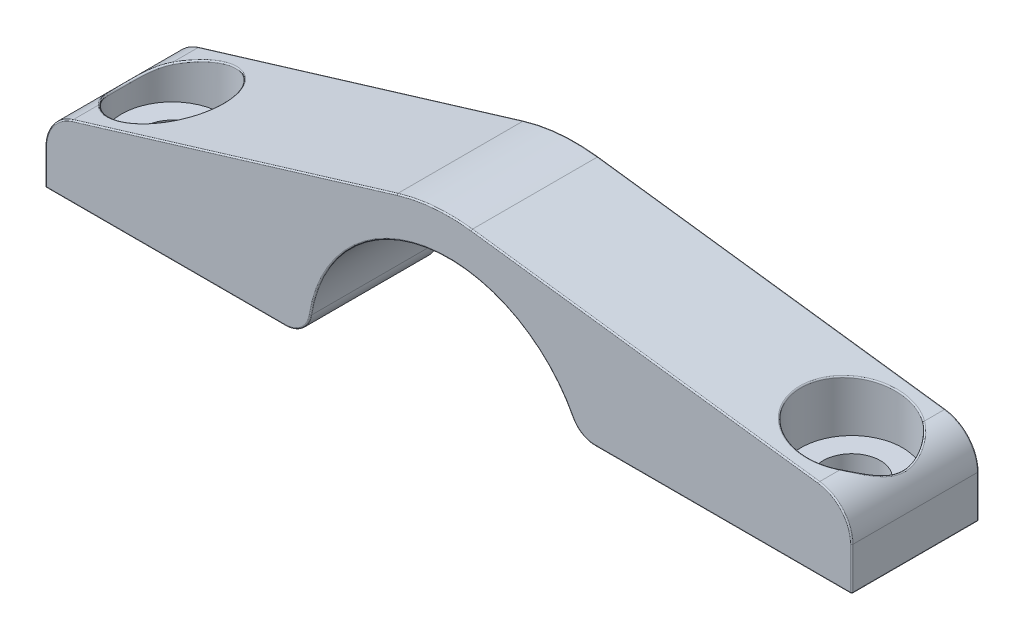
SolidWorks part; units mm, degrees
material "Сплав 2024"
ref_plane "Спереди" through (0, 0, 0) normal (0, 0, 1) x (1, 0, 0)
ref_plane "Сверху" through (0, 0, 0) normal (0, 1, 0) x (1, 0, 0)
ref_plane "Справа" through (0, 0, 0) normal (1, 0, 0) x (0, 0, -1)
sketch "Эскиз1" plane through (0, 0, 0) normal (0, 0, 1) x (1, 0, 0)
  line L0 (-50.7044, 0) -> (94.5195, 0) construction
  line L1 (0, 39.6279) -> (0, -47.9421) construction
  line L2 (-31.75, 5) -> (-4.0634, 13.3973)
  line L4 (-31.75, 5) -> (-31.75, 0)
  line L5 (-31.75, 0) -> (-11, 0)
  line L6 (31.75, 10) -> (31.75, 4)
  line L7 (-31.75, 5) -> (17.9945, 5) construction
  line L8 (-31.75, 0) -> (31.75, 10) construction
  line L9 (31.75, 10) -> (1.8004, 13.8838)
  line L10 (46.3702, 4) -> (-24.3242, 4) construction
  line L11 (31.75, 4) -> (10.247, 4)
  arc A0 (-11, 0) -> (10.247, 4) centre (0, 0) cw
  arc A1 (-4.0634, 13.3973) -> (1.8004, 13.8838) centre (0, 0) cw
  point P10 (0, 5)
  dimension "D1" = 11
  dimension "D2" = 3
  dimension "D3" = 63.5
  dimension "D4" = 5
  dimension "D5" = 31.75
  dimension "D6" = 4
  dimension "D7" = 6
extrude "Бобышка-Вытянуть1" add sketch "Эскиз1" along normal blind 10
fillet "Скругление1" [suppressed] radius 3
ref_plane "Плоскость1" through (0, 7, 0) normal (0, 1, 0) x (1, 0, 0)
sketch "Эскиз2" plane through (0, 7, 0) normal (0, 1, 0) x (1, 0, 0)
  line L0 (-31.75, -5) -> (-11, -5) construction
  line L1 (-31.75, -10) -> (-31.75, 0) construction
  line L2 (-11, -10) -> (-11, 0) construction
  line L3 (-26.75, -10) -> (-26.75, 0) construction
  dimension "D1" = 5
hole_wizard "Цековка для винта с внутренним шестигранником M42" positions "Эскиз6" profile "Эскиз5" counterbore size "M4" standard "Ansi Metric" end condition through all
sketch "Эскиз6" plane through (0, 7, 0) normal (0, 1, 0) x (1, 0, 0)
  line L0 (-31.75, -5) -> (-11, -5) construction
  line L1 (-26.75, -10) -> (-26.75, 0) construction
  point P0 (-26.75, -5)
sketch "Эскиз5" plane through (-26.75, 7, 5) normal (1, 0, 0) x (0, 0, -1)
  line L0 (0, 0) -> (0, 7)
  line L1 (0, 7) -> (2.25, 7)
  line L3 (2.25, 7) -> (2.25, 4)
  line L4 (2.25, 4) -> (4, 4)
  line L5 (4, 4) -> (4, 0)
  line L7 (4, 0) -> (0, 0)
  line L11 (0, -6.35) -> (0, 107.95) construction
  dimension "Диаметр сквозного отверстия" = 4.5
  dimension "Глубина сквозного отверстия" = 7
  dimension "Диаметр цековки" = 8
  dimension "Глубина цековки" = 4
hole_wizard "Цековка для винта с внутренним шестигранником M43" positions "Эскиз8" profile "Эскиз7" counterbore size "M4" standard "Ansi Metric" end condition through all
sketch "Эскиз8" plane through (0, 7, 0) normal (0, 1, 0) x (1, 0, 0)
  point P0 (-26.75, -5)
sketch "Эскиз7" plane through (-26.75, 7, 5) normal (1, 0, 0) x (0, 0, 1)
  line L0 (0, 0) -> (0, 7)
  line L1 (0, 7) -> (2.25, 7)
  line L3 (2.25, 7) -> (2.25, 4)
  line L4 (2.25, 4) -> (4, 4)
  line L5 (4, 4) -> (4, 0)
  line L7 (4, 0) -> (0, 0)
  line L11 (0, -6.35) -> (0, 107.95) construction
  dimension "Диаметр сквозного отверстия" = 4.5
  dimension "Глубина сквозного отверстия" = 7
  dimension "Диаметр цековки" = 8
  dimension "Глубина цековки" = 4
ref_plane "Плоскость2" through (0, 11, 0) normal (0, -1, 0) x (-1, 0, 0)
sketch "Эскиз9" plane through (0, 11, 0) normal (0, -1, 0) x (-1, 0, 0)
  line L0 (-31.75, -5) -> (-10.247, -5) construction
  line L1 (-31.75, -10) -> (-31.75, 0) construction
  line L2 (-10.247, -10) -> (-10.247, 0) construction
  line L3 (-26.75, 0) -> (-26.75, -10) construction
  dimension "D1" = 5
hole_wizard "Цековка для винта с внутренним шестигранником M44" positions "Эскиз11" profile "Эскиз10" counterbore size "M4" standard "Ansi Metric" end condition through all
sketch "Эскиз11" plane through (0, 11, 0) normal (0, -1, 0) x (-1, 0, 0)
  line L0 (-26.75, 0) -> (-26.75, -10) construction
  line L1 (-31.75, -5) -> (-10.247, -5) construction
  point P0 (-26.75, -5)
sketch "Эскиз10" plane through (26.75, 11, 5) normal (1, 0, 0) x (0, 0, 1)
  line L0 (0, 0) -> (0, 11)
  line L1 (0, 11) -> (2.25, 11)
  line L3 (2.25, 11) -> (2.25, 4)
  line L4 (2.25, 4) -> (4, 4)
  line L5 (4, 4) -> (4, 0)
  line L7 (4, 0) -> (0, 0)
  line L11 (0, -6.35) -> (0, 107.95) construction
  dimension "Диаметр сквозного отверстия" = 4.5
  dimension "Глубина сквозного отверстия" = 11
  dimension "Диаметр цековки" = 8
  dimension "Глубина цековки" = 4
hole_wizard "Цековка для винта с внутренним шестигранником M45" positions "Эскиз13" profile "Эскиз12" counterbore size "M4" standard "Ansi Metric" end condition through all
sketch "Эскиз13" plane through (0, 11, 0) normal (0, -1, 0) x (-1, 0, 0)
  line L0 (-31.75, -5) -> (-10.247, -5) construction
  line L1 (-26.75, 0) -> (-26.75, -10) construction
  point P0 (-26.75, -5)
sketch "Эскиз12" plane through (26.75, 11, 5) normal (1, 0, 0) x (0, 0, -1)
  line L0 (0, 0) -> (0, 3)
  line L1 (0, 3) -> (2.25, 3)
  line L3 (2.25, 3) -> (2.25, 4)
  line L4 (2.25, 4) -> (4, 4)
  line L5 (4, 4) -> (4, 0)
  line L7 (4, 0) -> (0, 0)
  line L11 (0, -6.35) -> (0, 107.95) construction
  dimension "Диаметр сквозного отверстия" = 4.5
  dimension "Глубина сквозного отверстия" = 3
  dimension "Диаметр цековки" = 8
  dimension "Глубина цековки" = 4
fillet "Скругление4" radius 2 2 edges at (10.247, 4, 5) (-11, 0, 5)
fillet "Скругление2" radius 3 2 edges at (-31.75, 5, 5) (31.75, 10, 5)
fillet "Скругление3" radius 0.1 32 edges at (30.7465, 9.6031, 5.1671) (-30.7258, 5.0324, 4.5607) (-31.75, 0, 5) (-26.75, 0, 7.25) (31.75, 4, 5) (24.5, 4, 5) (-22.2976, 0, 0) (-1.7811, 10.8548, 0) (21.6413, 4, 0) (31.75, 5.682, 0) (31.0036, 9.3441, 0) (15.4681, 12.1114, 0) (-1.1574, 13.9521, 0) (-16.8421, 9.5216, 0) (-31.1596, 4.5621, 0) (-31.75, 1.3875, 0) (-1.1574, 13.9521, 10) (15.4681, 12.1114, 10) (31.0036, 9.3441, 10) (31.75, 5.682, 10) (21.6413, 4, 10) (-1.7811, 10.8548, 10) (-22.2976, 0, 10) (-31.75, 1.3875, 10) (-31.1596, 4.5621, 10) (-16.8421, 9.5216, 10) (22.75, 11.1671, 5) (-22.75, 7.7297, 5) (-11.5443, 0.4809, 0) (10.4948, 4.2903, 0) (10.4948, 4.2903, 10) (-11.5443, 0.4809, 10)
